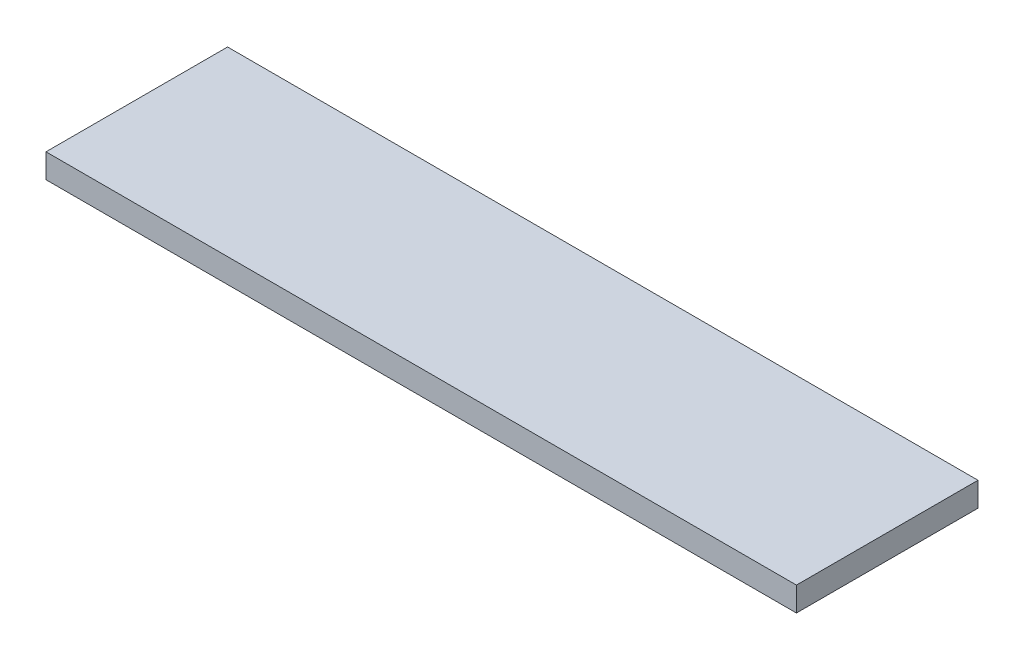
SolidWorks part; units mm, degrees
ref_plane "Front Plane" through (0, 0, 0) normal (0, 0, 1) x (1, 0, 0)
ref_plane "Top Plane" through (0, 0, 0) normal (0, 1, 0) x (1, 0, 0)
ref_plane "Right Plane" through (0, 0, 0) normal (1, 0, 0) x (0, 0, -1)
sketch "Sketch1" plane through (0, 0, 0) normal (0, 1, 0) x (1, 0, 0)
  line L1 (0, 0) -> (62, 0)
  line L2 (0, 0) -> (0, 15)
  line L3 (0, 15) -> (62, 15)
  line L4 (62, 0) -> (62, 15)
  dimension "D1" = 62
  dimension "D2" = 15
extrude "Boss-Extrude1" add sketch "Sketch1" along normal blind 2
